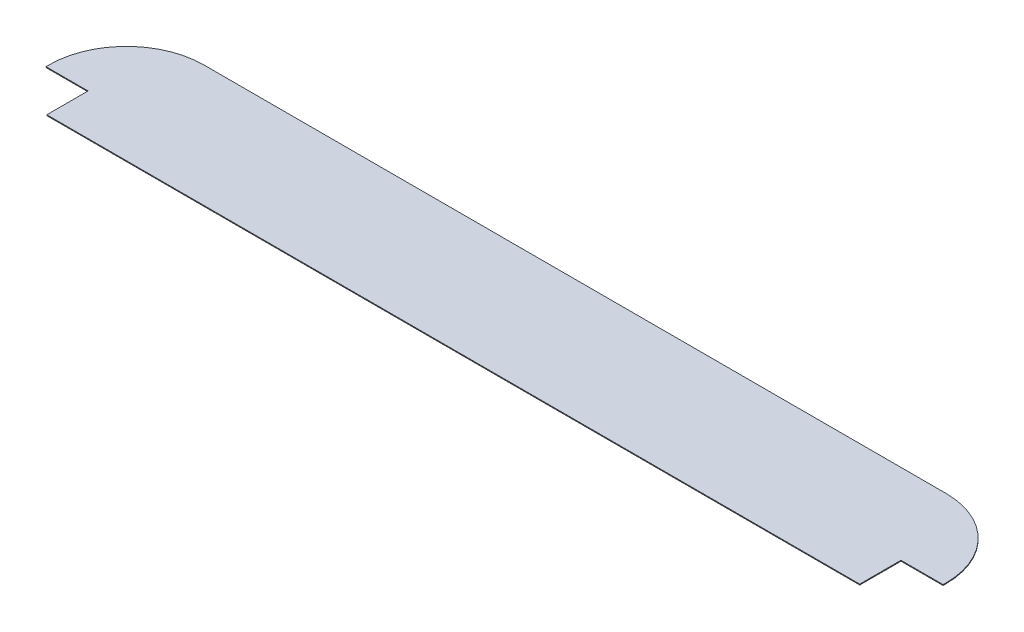
SolidWorks part; units mm, degrees
material "AISI 1020 Steel, Cold Rolled"
ref_plane "Front Plane" through (0, 0, 0) normal (0, 0, 1) x (1, 0, 0)
ref_plane "Top Plane" through (0, 0, 0) normal (0, 1, 0) x (1, 0, 0)
ref_plane "Right Plane" through (0, 0, 0) normal (1, 0, 0) x (0, 0, -1)
sketch "Sketch1" plane through (0, 0, 0) normal (0, 1, 0) x (1, 0, 0)
  line L1 (-455.05, -59) -> (333.35, -59)
  line L2 (-495.85, -19) -> (-495.85, -16)
  line L3 (-420.85, 59) -> (299.15, 59)
  line L4 (374.15, -19) -> (374.15, -16)
  line L5 (-455.05, -71.7572) -> (374.15, 59) construction
  line L6 (-495.85, 59) -> (333.35, -39.6645) construction
  line L9 (-495.85, -19) -> (-455.05, -19)
  line L10 (-455.05, -59) -> (-455.05, -19)
  line L13 (374.15, -19) -> (333.35, -19)
  line L14 (333.35, -59) -> (333.35, -19)
  arc A0 (-495.85, -16) -> (-420.85, 59) centre (-420.85, -16) cw
  arc A1 (299.15, 59) -> (374.15, -16) centre (299.15, -16) cw
  point P0 (0, 0)
  dimension "D7" = 75
  dimension "D8" = 75
  dimension "D1" = 870
  dimension "D3" = 40.8
  dimension "D4" = 40
  dimension "D5" = 40.8
  dimension "D6" = 40
sheet metal parameters "Sheet-Metal1" thickness 0.8 parameters "D1"=0.8
base flange "Base-Flange1" sketch "Sketch1" thickness 0.8 reverse thickness direction no parameters "D1"=0.8
flat pattern "Flat-Pattern1" [suppressed]
sketch "Bend-Lines1" plane through (0, 0, 0) normal (0, 1, 0) x (-1, 0, 0)
